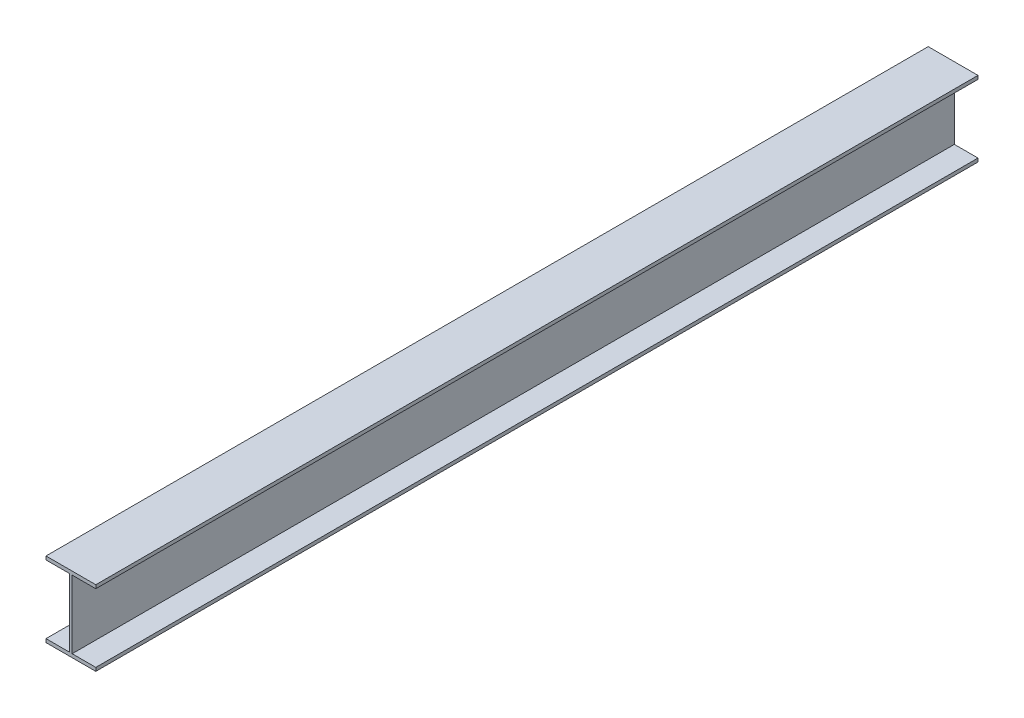
SolidWorks part; units mm, degrees
material "ASTM A992 Steel"
ref_plane "Front" through (0, 0, 0) normal (0, 0, 1) x (1, 0, 0)
ref_plane "Top" through (0, 0, 0) normal (0, 1, 0) x (1, 0, 0)
ref_plane "Right" through (0, 0, 0) normal (1, 0, 0) x (0, 0, -1)
sketch "Sketch1" plane through (0, 0, 0) normal (0, 0, 1) x (1, 0, 0)
  line L0 (0, -0.0002) -> (101.6, -0.0002)
  line L1 (101.6, -0.0002) -> (101.6, -7.1122)
  line L2 (101.6, -7.1122) -> (53.408, -7.1122)
  line L3 (53.408, -7.1122) -> (53.408, -146.0502)
  line L4 (53.408, -146.0502) -> (101.6, -146.0502)
  line L5 (101.6, -146.0502) -> (101.6, -153.1622)
  line L6 (101.6, -153.1622) -> (0, -153.1622)
  line L7 (0, -153.1622) -> (0, -146.0502)
  line L8 (0, -146.0502) -> (47.566, -146.0502)
  line L9 (47.566, -146.0502) -> (47.566, -7.1122)
  line L10 (47.566, -7.1122) -> (0, -7.1122)
  line L11 (0, -7.1122) -> (0, -0.0002)
  line L12 (50.8, -0.0002) -> (50.8, -153.1622) construction
  dimension "D1" = 5.842
  dimension "D2" = 7.112
  dimension "D3" = 7.112
  dimension "D4" = 7.112
  dimension "D5" = 153.162
  dimension "D6" = 50.8
  dimension "D7" = 50.8
  dimension "D8" = 47.566
extrude "Boss-Extrude1" add sketch "Sketch1" along normal blind 1800
